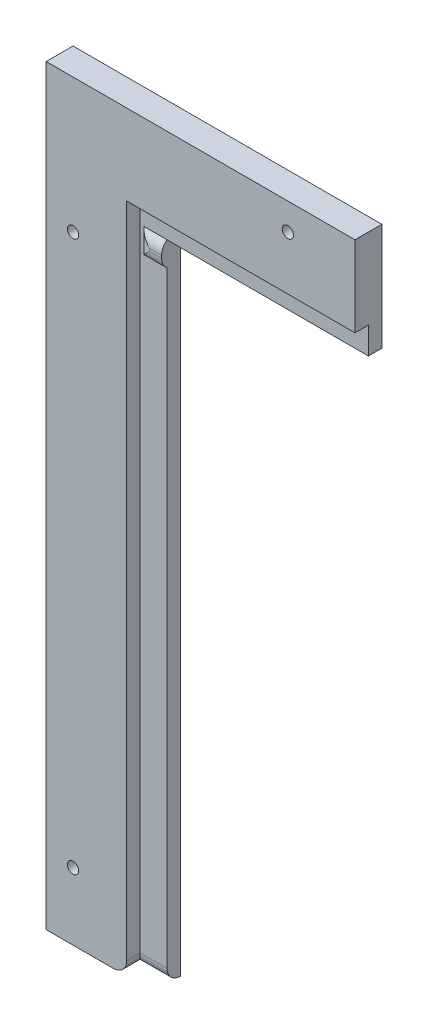
SolidWorks part; units mm, degrees
ref_plane "Front Plane" through (0, 0, 0) normal (0, 0, 1) x (1, 0, 0)
ref_plane "Top Plane" through (0, 0, 0) normal (0, 1, 0) x (1, 0, 0)
ref_plane "Right Plane" through (0, 0, 0) normal (1, 0, 0) x (0, 0, -1)
sketch "Sketch4" plane through (0, 0, 0) normal (0, 0, 1) x (1, 0, 0)
  line L1 (15, 125) -> (-15, 125)
  line L2 (15, 125) -> (15, -125)
  line L3 (15, -125) -> (-15, -125)
  line L4 (-15, 125) -> (-15, -125)
  line L5 (15, 125) -> (-15, -125) construction
  line L6 (15, -125) -> (-15, 125) construction
  line L11 (-15, 125) -> (100, 125)
  line L12 (-15, 125) -> (-15, 155)
  line L13 (-15, 155) -> (100, 155)
  line L14 (100, 125) -> (100, 155)
  point P0 (0, 0)
  dimension "D1" = 30
  dimension "D2" = 30
  dimension "D3" = 250
  dimension "D4" = 85
extrude "Boss-Extrude3" add sketch "Sketch4" along normal mid plane 10 contours L11 L14 L13 L12 L1 | L1 L4 L3 L2 region at (0, 0, 0) region at (42.5, 140, 0)
ref_plane "Plane1" through (15, 125, -5) normal (0, -1, 0) x (-1, 0, 0)
sketch "Sketch5" plane through (15, 125, -5) normal (0, -1, 0) x (1, 0, 0)
  line L0 (85, 10) -> (85, 0) construction
  line L1 (0, 0) -> (85, 0)
  line L2 (0, 0) -> (0, 5)
  line L3 (0, 5) -> (85, 5)
  line L4 (85, 0) -> (85, 5)
  dimension "D1" = 5
extrude "Boss-Extrude4" add sketch "Sketch5" along normal blind 10
sketch "Sketch6" plane through (15, 0, 0) normal (1, 0, 0) x (0, 0, -1)
  line L0 (-5, -125) -> (5, -125) construction
  line L1 (5, 115) -> (0, 115)
  line L2 (5, 115) -> (5, -125)
  line L3 (5, -125) -> (0, -125)
  line L4 (0, 115) -> (0, -125)
extrude "Boss-Extrude5" add sketch "Sketch6" along normal blind 10
sketch "Sketch7" plane through (0, 0, 0) normal (0, 0, 1) x (1, 0, 0)
  line L1 (25, 115) -> (16.5, 115)
  line L2 (25, 115) -> (25, 106)
  line L3 (25, 106) -> (16.5, 106)
  line L4 (16.5, 115) -> (16.5, 106)
  dimension "D1" = 9
  dimension "D2" = 8.5
extrude "Boss-Extrude6" add sketch "Sketch7" along normal blind 2
fillet "Fillet2" radius 5 3 edges at (16.5, 110.5, 2) (20.75, 115, 2) (20.75, 106, 2)
fillet "Fillet3" radius 5 2 edges at (15, -125, 2.5) (20, -125, 0)
sketch "Sketch8" plane through (0, 0, -5) normal (0, 0, -1) x (-1, 0, 0)
  line L0 (-100, 115) -> (-100, 155) construction
  line L1 (15, 155) -> (-100, 155) construction
  line L2 (15, -125) -> (15, 155) construction
  line L3 (-10, -125) -> (15, -125) construction
  circle A0 centre (5, -100) radius 2.1
  circle A1 centre (5, 105) radius 2.1
  circle A2 centre (-75, 145) radius 2.1
  point P14 (0, 0)
  point P16 (3.729, -101.815)
  dimension "D3" = 4.2
  dimension "D4" = 4.2
  dimension "D9" = 4.2
  dimension "D1" = 25
  dimension "D2" = 10
  dimension "D5" = 10
  dimension "D6" = 50
  dimension "D7" = 25
  dimension "D8" = 10
extrude "Cut-Extrude1" cut sketch "Sketch8" against normal blind 432
sketch "Sketch9" plane through (0, 0, -5) normal (0, 0, -1) x (-1, 0, 0)
  circle A0 centre (-75, 145) radius 3.6
  circle A2 centre (5, 105) radius 3.6
  circle A3 centre (5, -100) radius 3.6
  dimension "D1" = 7.2
  dimension "D2" = 7.2
  dimension "D3" = 7.2
extrude "Cut-Extrude2" cut sketch "Sketch9" against normal blind 4
